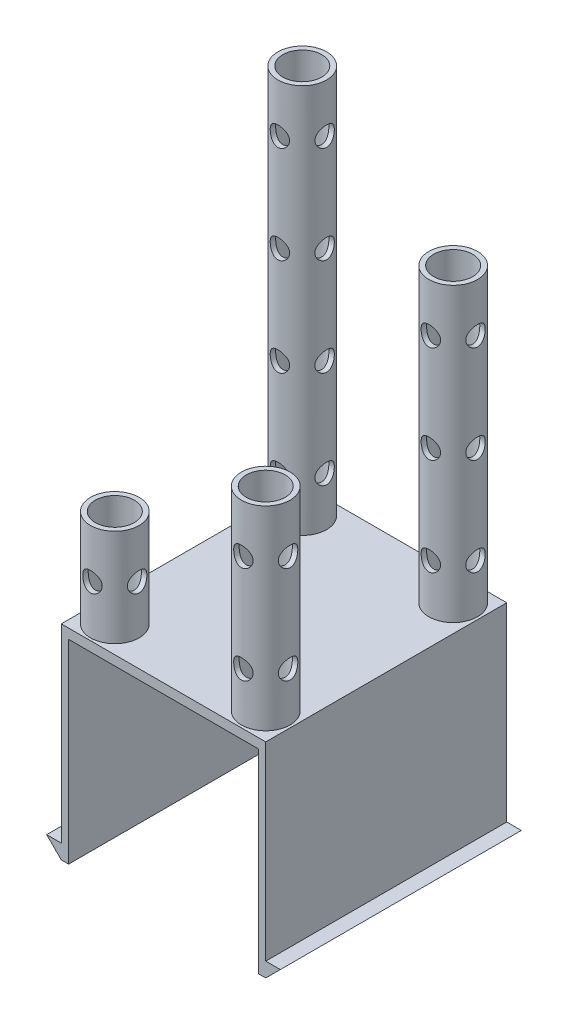
SolidWorks part; units mm, degrees
note: The reader was unsure of these and kept them because the rebuilt part matched: shared geometry of "Sketch1<2>", "Sketch10<3>", "Sketch10<4>".
ref_plane "Front Plane" through (0, 0, 0) normal (0, 0, 1) x (1, 0, 0)
ref_plane "Top Plane" through (0, 0, 0) normal (0, 1, 0) x (1, 0, 0)
ref_plane "Right Plane" through (0, 0, 0) normal (1, 0, 0) x (0, 0, -1)
sketch "Sketch1" plane through (0, 0, 0) normal (0, 1, 0) x (1, 0, 0)
  circle A0 centre (0, 0) radius 27.5
  circle A1 centre (0, 0) radius 30
  dimension "D1" = 55
  dimension "D2" = 60
extrude "Boss-Extrude1" add sketch "Sketch1" along normal blind 100
extrude "Boss-Extrude2" add sketch "Sketch1<2>" along normal blind 5 contours A0
sketch "Sketch1<2>" plane through (0, 0, 0) normal (0, 1, 0) x (1, 0, 0) same geometry as "Sketch1"
sketch "Sketch2" plane through (0, 0, 0) normal (0, -1, 0) x (1, 0, 0)
  line L1 (-19.5, 24.75) -> (-21, 24.75)
  line L2 (-19.5, 24.75) -> (-19.5, -24.75)
  line L3 (-19.5, -24.75) -> (-21, -24.75)
  line L4 (-21, 24.75) -> (-21, -24.75)
  line L5 (21, 24.75) -> (19.5, 24.75)
  line L6 (21, 24.75) -> (21, -24.75)
  line L7 (21, -24.75) -> (19.5, -24.75)
  line L8 (19.5, 24.75) -> (19.5, -24.75)
  circle A0 centre (0, 0) radius 30 construction
  point P8 (-20.25, 24.75)
  dimension "D1" = 1.5
  dimension "D2" = 42
  dimension "D3" = 21
  dimension "D4" = 49.5
  dimension "D5" = 24.75
extrude "Boss-Extrude3" add sketch "Sketch2" along normal blind 40
sketch "Sketch3" plane through (0, 0, 0) normal (0, -1, 0) x (1, 0, 0)
  line L1 (21, 24.75) -> (-21, 24.75)
  line L2 (21, 24.75) -> (21, -24.75)
  line L3 (21, -24.75) -> (-21, -24.75)
  line L4 (-21, 24.75) -> (-21, -24.75)
extrude "Boss-Extrude4" add sketch "Sketch3" against normal blind 2
sketch "Sketch4" plane through (0, 0, -24.75) normal (0, 0, -1) x (-1, 0, 0)
  line L0 (21, -40) -> (24, -37)
  line L1 (24, -37) -> (21, -37)
  line L2 (21, -40) -> (21, 2) construction
  line L3 (21, -37) -> (21, -40)
  line L4 (-21, -40) -> (-24, -37)
  line L5 (-24, -37) -> (-21, -37)
  line L6 (-21, -40) -> (-21, 2) construction
  line L7 (-21, -37) -> (-21, -40)
  dimension "D1" = 45
  dimension "D2" = 45
  dimension "D3" = 3
  dimension "D4" = 3
extrude "Boss-Extrude5" add sketch "Sketch4" against normal up to surface (49.5 mm away) up to face at (19.1513, -12.6667, 24.75)
sketch "Sketch5" plane through (0, 2, 0) normal (0, 1, 0) x (1, 0, 0)
  line L1 (34.8385, 32.8261) -> (-38.3601, 32.8261)
  line L2 (34.8385, 32.8261) -> (34.8385, -30.5623)
  line L3 (34.8385, -30.5623) -> (-38.3601, -30.5623)
  line L4 (-38.3601, 32.8261) -> (-38.3601, -30.5623)
extrude "Cut-Extrude1" cut sketch "Sketch5" along normal blind 100
sketch "Sketch7" plane through (0, 2, 0) normal (0, 1, 0) x (1, 0, 0)
  line L1 (-27.6991, 24.75) -> (28.8977, 24.75)
  line L2 (-27.6991, 24.75) -> (-27.6991, 30.5623)
  line L3 (-27.6991, 30.5623) -> (28.8977, 30.5623)
  line L4 (28.8977, 24.75) -> (28.8977, 30.5623)
  line L5 (21, 24.75) -> (34.4105, 24.75)
  line L6 (21, 24.75) -> (21, -29.053)
  line L7 (21, -29.053) -> (34.4105, -29.053)
  line L8 (34.4105, 24.75) -> (34.4105, -29.053)
  line L9 (25.963, -24.75) -> (-25.4353, -24.75)
  line L10 (25.963, -24.75) -> (25.963, -33.2758)
  line L11 (25.963, -33.2758) -> (-25.4353, -33.2758)
  line L12 (-25.4353, -24.75) -> (-25.4353, -33.2758)
  line L13 (-21, 24.75) -> (-38.5247, 24.75)
  line L14 (-21, 24.75) -> (-21, -26.2307)
  line L15 (-21, -26.2307) -> (-38.5247, -26.2307)
  line L16 (-38.5247, 24.75) -> (-38.5247, -26.2307)
  line L17 (-21, -24.75) -> (-21, 24.75) construction
  line L18 (21, -21.4243) -> (21, -24.75) construction
  point P19 (0, 0)
  point P20 (0, 0)
  point P22 (0, 0)
  point P23 (0, 0)
  arc M18 (21, -21.4243) -> (21, 21.4243) centre (0, 0) ccw
  arc M21 (16.954, 24.75) -> (-16.954, 24.75) centre (0, 0) ccw
  arc M24 (-21, 21.4243) -> (-21, -21.4243) centre (0, 0) ccw
  arc M27 (-16.954, -24.75) -> (16.954, -24.75) centre (0, 0) ccw
extrude "Cut-Extrude2" cut sketch "Sketch7" against normal blind 5 contours L13 L16 L15 L12 L9 L14 L1 M24 | L14 M24 | L1 M21 | L6 M18 | L11 L9 M27 | L11 M27
sketch "Sketch8" plane through (0, 2, 0) normal (0, 1, 0) x (1, 0, 0)
  line L0 (-21, -24.75) -> (-21, 24.75) construction
  line L1 (-21, 24.75) -> (21, 24.75) construction
  line L2 (21, -24.75) -> (-21, -24.75) construction
  line L3 (21, 24.75) -> (21, -24.75) construction
  circle A0 centre (-15.5, 19.25) radius 5
  circle A1 centre (15.5, 19.25) radius 5
  circle A2 centre (-15.5, -19.25) radius 5
  circle A3 centre (15.5, -19.25) radius 5
  circle A4 centre (-15.5, 19.25) radius 4
  circle A5 centre (15.5, 19.25) radius 4
  circle A6 centre (15.5, -19.25) radius 4
  circle A7 centre (-15.5, -19.25) radius 4
  dimension "D1" = 10
  dimension "D5" = 8
  dimension "D2" = 5.5
  dimension "D3" = 5.5
  dimension "5.5" = 5.5
  dimension "D4" = 5.5
extrude "Boss-Extrude6" add sketch "Sketch8" along normal blind 80
sketch "Sketch9" plane through (-21, 0, 0) normal (-1, 0, 0) x (0, 0, 1)
  line L0 (-15.25, 82) -> (-23.25, 82) construction
  line L1 (-24.25, 82) -> (-24.25, 2) construction
  circle A0 centre (-19.25, 72) radius 2
  dimension "D1" = 4
  dimension "D2" = 10
  dimension "D3" = 5
extrude "Cut-Extrude3" cut sketch "Sketch9" against normal blind 20
pattern_circular "CirPattern1" count 4 over 360 about axis through (-15.5, 82, -19.25) along (0, 1, 0) of "Cut-Extrude3"
pattern_linear "LPattern1" count 4 spacing 20 along (0, -1, 0) of "CirPattern1", "Cut-Extrude3"
pattern_linear "LPattern2" count 2 spacing 38.5 along (0, 0, 1) of "LPattern1", "Cut-Extrude3", "CirPattern1"
pattern_linear "LPattern3" count 2 spacing 31 along (1, 0, 0) of "LPattern2", "Cut-Extrude3", "CirPattern1", "LPattern1"
sketch "Sketch10" plane through (0, 82, 0) normal (0, 1, 0) x (1, 0, 0)
  line L1 (24.518, 28.3984) -> (5.2688, 28.3984)
  line L2 (24.518, 28.3984) -> (24.518, 10.1992)
  line L3 (24.518, 10.1992) -> (5.2688, 10.1992)
  line L4 (5.2688, 28.3984) -> (5.2688, 10.1992)
  line L5 (30.9577, -6.4602) -> (5.2688, -6.4602)
  line L6 (30.9577, -6.4602) -> (30.9577, -27.7393)
  line L7 (30.9577, -27.7393) -> (5.2688, -27.7393)
  line L8 (5.2688, -6.4602) -> (5.2688, -27.7393)
  line L9 (-28.1199, -9.54) -> (-6.8407, -9.54)
  line L10 (-28.1199, -9.54) -> (-28.1199, -27.7393)
  line L11 (-28.1199, -27.7393) -> (-6.8407, -27.7393)
  line L12 (-6.8407, -9.54) -> (-6.8407, -27.7393)
  circle M1 centre (15.5, 19.25) radius 5
  circle M2 centre (15.5, 19.25) radius 4
extrude "Cut-Extrude4" cut sketch "Sketch10" against normal blind 20 contours M1 M2
extrude "Cut-Extrude5" cut sketch "Sketch10<3>" against normal blind 40 contours L5 L8 L7 L6
sketch "Sketch10<3>" plane through (0, 82, 0) normal (0, 1, 0) x (1, 0, 0) same geometry as "Sketch10"
extrude "Cut-Extrude6" cut sketch "Sketch10<4>" against normal blind 60 contours L12 L9 L10 L11
sketch "Sketch10<4>" plane through (0, 82, 0) normal (0, 1, 0) x (1, 0, 0) same geometry as "Sketch10"
